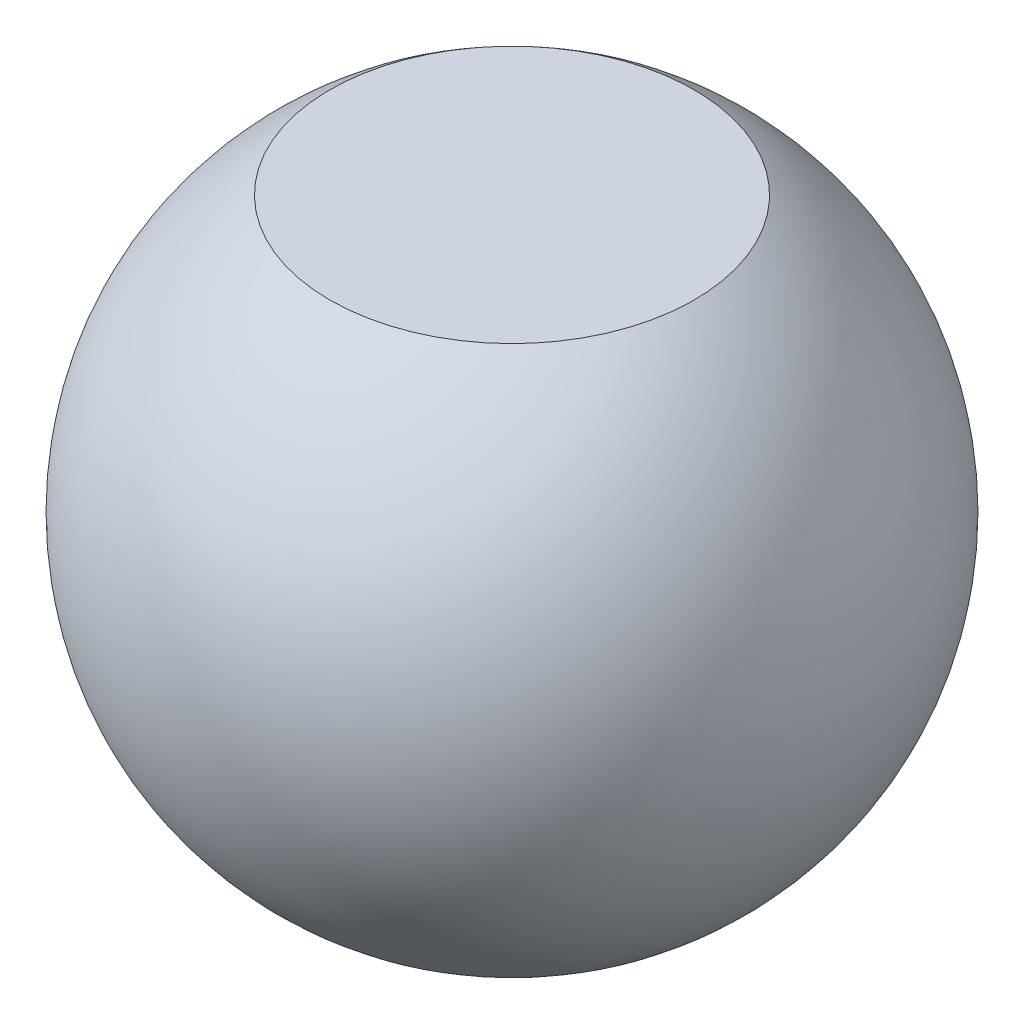
SolidWorks part; units mm, degrees
ref_plane "Plan de face" through (0, 0, 0) normal (0, 0, 1) x (1, 0, 0)
ref_plane "Plan de dessus" through (0, 0, 0) normal (0, 1, 0) x (1, 0, 0)
ref_plane "Plan de droite" through (0, 0, 0) normal (1, 0, 0) x (0, 0, -1)
sketch "Esquisse1" plane through (0, 0, 0) normal (0, 0, 1) x (1, 0, 0)
  line L0 (0, 15) -> (0, -15)
  line L1 (32.2713, 18) -> (-32.4086, 18) construction
  line L2 (0, 15) -> (-9.9499, 15)
  line L3 (0, -15) -> (-9.9499, -15)
  arc A0 (-9.9499, 15) -> (-9.9499, -15) centre (0, 0) ccw
  dimension "D1" = 18
  dimension "D2" = 30
revolve "Révolution1" add sketch "Esquisse1" angle 360 about L0
sketch "Esquisse2" plane through (0, 0, 0) normal (1, 0, 0) x (0, 0, -1)
  circle A0 centre (0, 0) radius 3
  dimension "D1" = 6
extrude "Enlèv. mat.-Extru.1" cut sketch "Esquisse2" against normal through all
sketch "Esquisse3" plane through (0, 0, 0) normal (1, 0, 0) x (0, 0, -1)
  circle A0 centre (0, -10.5) radius 1.5
  dimension "D2" = 3
  dimension "D1" = 10.5
extrude "Enlèv. mat.-Extru.2" cut sketch "Esquisse3" against normal through all
ref_point "Point1"
ref_point "Point2"
ref_axis "Axe1" through (0, 15, 0) along (0, -1, 0)
ref_plane "Plan1" through (0, -18.5, 0) normal (0, -1, 0) x (-1, 0, 0)
ref_point "Point3"
ref_plane "Plan2" through (0, 18.5, 0) normal (0, 1, 0) x (1, 0, 0)
ref_point "Point4"
